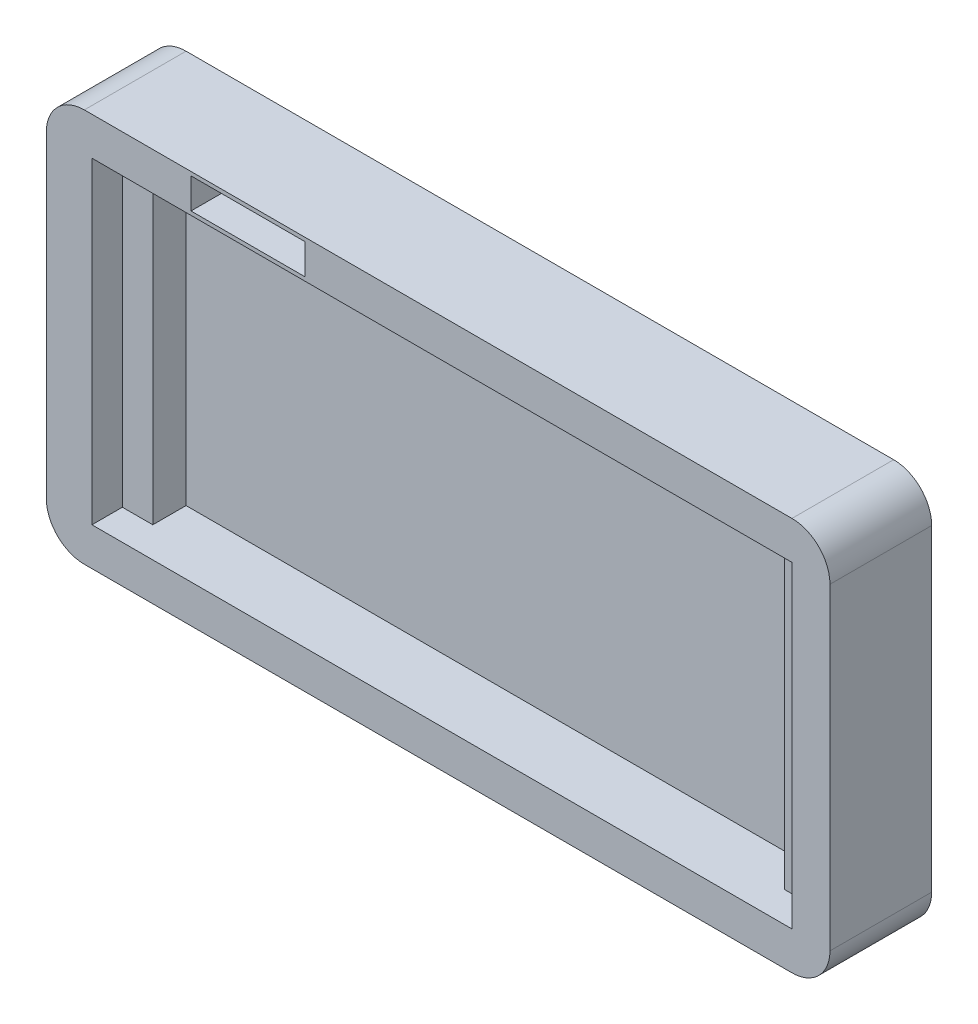
SolidWorks part; units mm, degrees
ref_plane "Front Plane" through (0, 0, 0) normal (0, 0, 1) x (1, 0, 0)
ref_plane "Top Plane" through (0, 0, 0) normal (0, 1, 0) x (1, 0, 0)
ref_plane "Right Plane" through (0, 0, 0) normal (1, 0, 0) x (0, 0, -1)
sketch "Croquis1" plane through (0, 0, 0) normal (0, 0, 1) x (1, 0, 0)
  line L1 (-0.0577, 28.6511) -> (37.1623, 28.6511)
  line L2 (-0.0577, 28.6511) -> (-0.0577, 11.9511)
  line L3 (-0.0577, 11.9511) -> (37.1623, 11.9511)
  line L4 (37.1623, 28.6511) -> (37.1623, 11.9511)
  line L5 (0.5423, 28.4511) -> (36.9623, 28.4511) construction
  line L7 (36.9623, 28.4511) -> (36.9623, 12.1511) construction
  line L8 (36.9623, 12.1511) -> (0.5423, 12.1511) construction
  line L9 (0.5423, 12.1511) -> (0.5423, 28.4511) construction
  point P5 (37.3034, 11.752)
  point P7 (0.5423, 28.4511)
  point P8 (0.287, 28.9622)
  point P13 (37.2519, 12.1511)
  dimension "D1" = 0.2
  dimension "D2" = 0.6
  dimension "D3" = 0.2
  dimension "D4" = 0.2
extrude "Saliente-Extruir1" add sketch "Croquis1" along normal up to surface (3.35 mm away)
shell "Vaciado1" thickness 2
fillet "Redondeo1" radius 2 4 edges at (39.1623, 9.9511, 0.675) (-2.0577, 9.9511, 0.675) (-2.0577, 30.6511, 0.675) (39.1623, 30.6511, 0.675)
sketch "Croquis2" plane through (0, 0, 0) normal (0, 0, 1) x (1, 0, 0)
  line L0 (37.1623, 11.9511) -> (-0.0577, 11.9511) construction
  line L1 (-0.0577, 28.6511) -> (1.9423, 28.6511)
  line L2 (-0.0577, 28.6511) -> (-0.0577, 11.9511)
  line L3 (-0.0577, 11.9511) -> (1.9423, 11.9511)
  line L4 (1.9423, 28.6511) -> (1.9423, 11.9511)
  line L5 (-0.0577, 11.9511) -> (37.1623, 11.9511) construction
  line L6 (37.1623, 28.6511) -> (35.1623, 28.6511)
  line L7 (37.1623, 28.6511) -> (37.1623, 11.9511)
  line L8 (37.1623, 11.9511) -> (35.1623, 11.9511)
  line L9 (35.1623, 28.6511) -> (35.1623, 11.9511)
  dimension "D1" = 2
  dimension "D2" = 2
extrude "Saliente-Extruir2" add sketch "Croquis2" along normal up to surface (1.75 mm away)
sketch "Croquis6" plane through (0, 0, 1.75) normal (0, 0, 1) x (1, 0, 0)
  line L0 (37.1623, 11.9511) -> (-0.0577, 11.9511) construction
  line L1 (-0.0577, 28.6511) -> (0.3423, 28.6511)
  line L2 (-0.0577, 28.6511) -> (-0.0577, 11.9511)
  line L3 (-0.0577, 11.9511) -> (0.3423, 11.9511)
  line L4 (0.3423, 28.6511) -> (0.3423, 11.9511)
  line L5 (0.5423, 12.1511) -> (0.5423, 28.4511) construction
  dimension "D1" = 0.2
extrude "Saliente-Extruir5" add sketch "Croquis6" along normal up to vertex (1.6 mm away)
sketch "Croquis7" plane through (0, 0, 3.35) normal (0, 0, 1) x (1, 0, 0)
  line L0 (18.5523, 30.6511) -> (18.5523, 9.9777) construction
  line L1 (-0.0577, 30.6511) -> (37.1623, 30.6511) construction
  line L2 (39.1623, 20.3011) -> (-5.3544, 20.3011) construction
  line L3 (39.1623, 28.6511) -> (39.1623, 11.9511) construction
  line L9 (0.3423, 28.6511) -> (37.1623, 28.6511) construction
  line L10 (5.5523, 30.4511) -> (11.5523, 30.4511)
  line L11 (5.5523, 30.4511) -> (5.5523, 28.8511)
  line L12 (5.5523, 28.8511) -> (11.5523, 28.8511)
  line L13 (11.5523, 30.4511) -> (11.5523, 28.8511)
  line L14 (5.5523, 30.4511) -> (11.5523, 28.8511) construction
  line L15 (5.5523, 28.8511) -> (11.5523, 30.4511) construction
  point P8 (6.2005, 29.1357)
  point P10 (8.5523, 29.6511)
  point P16 (0, 0)
  point P17 (0, 0)
  dimension "D1" = 0.2
  dimension "D2" = 0.2
  dimension "D3" = 6
  dimension "D4" = 10
extrude "Cortar-Extruir1" cut sketch "Croquis7" against normal blind 3
sketch "Croquis10" plane through (0, 0, 0.35) normal (0, 0, 1) x (1, 0, 0)
  line L0 (11.5523, 30.4511) -> (5.5523, 30.4511) construction
  line L1 (12.5523, 28.8511) -> (4.5523, 28.8511)
  line L2 (12.5523, 28.8511) -> (12.5523, 30.4511)
  line L3 (12.5523, 30.4511) -> (4.5523, 30.4511)
  line L4 (4.5523, 28.8511) -> (4.5523, 30.4511)
  line L5 (12.5523, 28.8511) -> (4.5523, 30.4511) construction
  line L6 (12.5523, 30.4511) -> (4.5523, 28.8511) construction
  line L8 (11.5523, 28.8511) -> (11.5523, 30.4511) construction
  line L9 (5.5523, 30.4511) -> (5.5523, 28.8511) construction
  point P0 (8.5523, 29.6511)
  dimension "D1" = 1
  dimension "D2" = 1
extrude "Cortar-Extruir2" cut sketch "Croquis10" against normal blind 3
